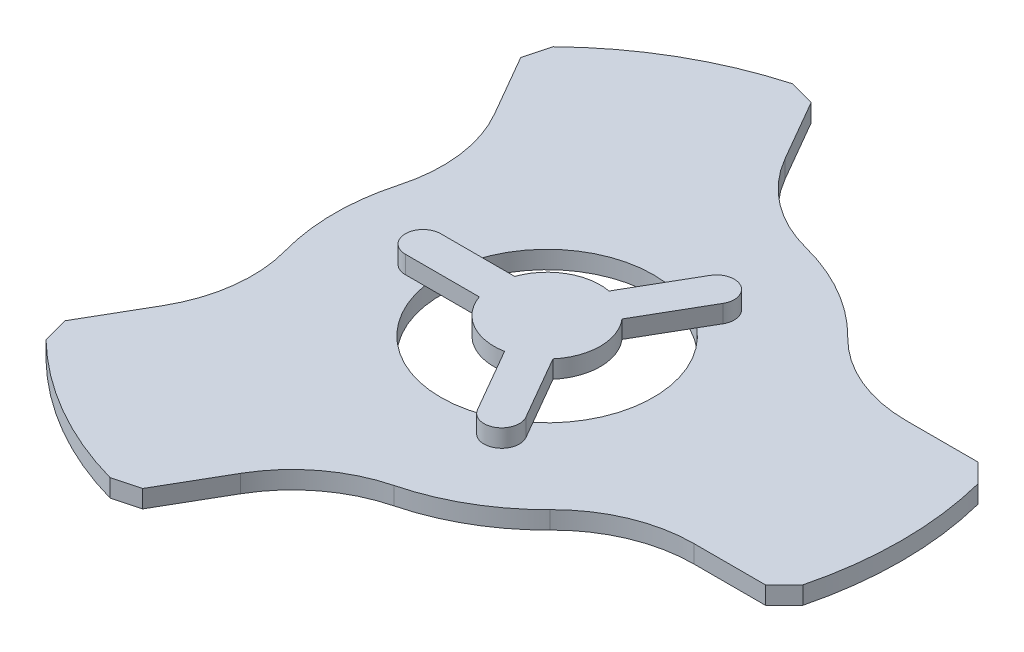
SolidWorks part; units mm, degrees
ref_plane "Front Plane" through (0, 0, 0) normal (0, 0, 1) x (1, 0, 0)
ref_plane "Top Plane" through (0, 0, 0) normal (0, 1, 0) x (1, 0, 0)
ref_plane "Right Plane" through (0, 0, 0) normal (1, 0, 0) x (0, 0, -1)
sketch "Sketch2" plane through (0, 0, 0) normal (0, 1, 0) x (1, 0, 0)
  line L8 (103.923, 60) -> (190.7878, 60)
  line L9 (103.923, -60) -> (190.7878, -60)
  line L10 (103.923, 60) -> (103.923, -60) construction
  line L11 (183.1982, 60) -> (193.8048, 49.3934)
  line L12 (103.923, 0) -> (200, 0) construction
  line L13 (183.1982, -60) -> (193.8048, -49.3934)
  circle A0 centre (0, 0) radius 60
  circle A1 centre (0, 0) radius 120
  arc A5 (190.7878, -60) -> (190.7878, 60) centre (0, 0) ccw
  point P20 (103.923, 0)
  dimension "D1" = 120
  dimension "D2" = 240
  dimension "D4" = 400
  dimension "D7" = 120
  dimension "D8" = 45
  dimension "D9" = 15
extrude "Boss-Extrude1" add sketch "Sketch2" along normal blind 10 contours A1 A0 region at (112.6326, 0, -30.1798)
extrude "Boss-Extrude2" add sketch "Sketch2<3>" along normal blind 10 contours A1 region at (155.5047, 0, 0)
sketch "Sketch2<3>" plane through (0, 0, 0) normal (0, 1, 0) x (1, 0, 0) same geometry as "Sketch2"
pattern_circular "CirPattern1" count 3 over 360 about axis through (0, 10, 0) along (0, -1, 0) of "Boss-Extrude2" reverse direction yes
fillet "Fillet1" radius 80 6 edges at (-103.923, 5, 60) (-103.923, 5, -60) (0, 5, -120) (103.923, 5, -60) (0, 5, 120) (103.923, 5, 60)
sketch "Sketch3" plane through (0, 10, 0) normal (0, 1, 0) x (1, 0, 0)
  line L0 (0, 0) -> (-70, 0) construction
  line L1 (0, -10) -> (-70, -10)
  line L2 (0, 10) -> (-70, 10)
  line L3 (8.6603, -5) -> (43.6603, 55.6218)
  line L4 (-8.6603, 5) -> (26.3397, 65.6218)
  line L5 (0, 0) -> (35, 60.6218) construction
  line L6 (-8.6603, -5) -> (26.3397, -65.6218)
  line L7 (8.6603, 5) -> (43.6603, -55.6218)
  line L8 (0, 0) -> (35, -60.6218) construction
  circle A0 centre (0, 0) radius 30
  arc A1 (0, -10) -> (0, 10) centre (0, 0) ccw
  arc A2 (-70, 10) -> (-70, -10) centre (-70, 0) ccw
  arc A3 (-8.6603, 5) -> (8.6603, -5) centre (0, 0) ccw
  arc A4 (43.6603, 55.6218) -> (26.3397, 65.6218) centre (35, 60.6218) ccw
  arc A5 (8.6603, 5) -> (-8.6603, -5) centre (0, 0) ccw
  arc A6 (26.3397, -65.6218) -> (43.6603, -55.6218) centre (35, -60.6218) ccw
  point P3 (-35, 0)
  point P9 (17.5, 30.3109)
  point P17 (17.5, -30.3109)
  point P23 (0, 0)
  circle M1 centre (0, 0) radius 60
  dimension "D1" = 60
  dimension "D3" = 10
  dimension "D2" = 70
  dimension "D4" = 3
extrude "Boss-Extrude3" add sketch "Sketch3" along normal blind 10 contours A5 L2 L4 | A1 L3 L7 | A3 L6 L1 | A1 A5 A3 | A1 L7 L3 A0 L4 L2 | A1 L1 L6 A0 L7 L3 | A3 L4 L2 A0 L1 L6 | L4 A0 L2 | L7 A0 L3 | L1 A0 L6 | A0 L2 L1 M1 | A0 L3 L4 M1 | A0 L6 L7 M1 | L6 A6 L7 M1 | L3 A4 L4 M1 | L2 A2 L1 M1 region at (9.4382, 10, 16.3475) region at (0, 10, 0) region at (-5.1678, 10, 8.9509) region at (-11.0803, 10, 19.1917) region at (-18.8764, 10, 0) region at (10.3356, 10, 0) region at (-44.5747, 10, 0) region at (22.2873, 10, 38.6028) region at (9.4382, 10, -16.3475) region at (22.1607, 10, 0) region at (-5.1678, 10, -8.9509) region at (-68.9232, 10, 0) region at (-11.0803, 10, -19.1917) region at (34.4616, 10, 59.6892) region at (22.2873, 10, -38.6028) region at (34.4616, 10, -59.6892)
